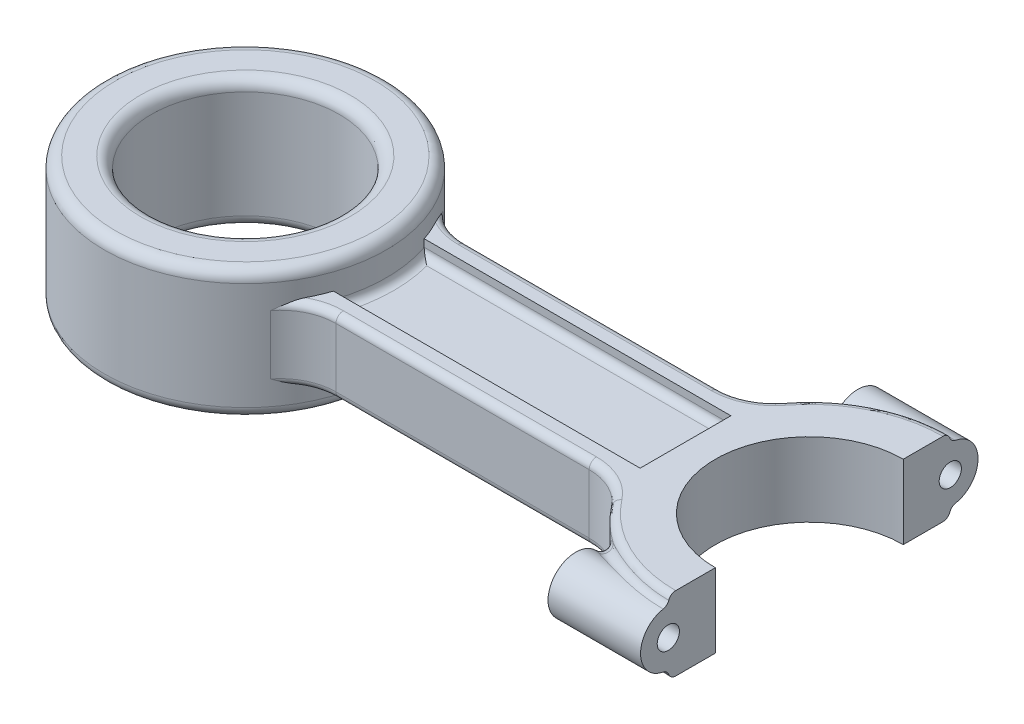
SolidWorks part; units mm, degrees
ref_plane "Front Plane" through (0, 0, 0) normal (0, 0, 1) x (1, 0, 0)
ref_plane "Top Plane" through (0, 0, 0) normal (0, 1, 0) x (1, 0, 0)
ref_plane "Right Plane" through (0, 0, 0) normal (1, 0, 0) x (0, 0, -1)
sketch "Sketch2" plane through (0, 0, 0) normal (0, 1, 0) x (1, 0, 0)
  line L0 (0, 0) -> (152.4, 0) construction
  line L1 (152.4, 38.1) -> (152.4, 25.4)
  line L2 (110.4076, -17.5) -> (41.9924, -17.5)
  line L4 (110.4076, 17.5) -> (41.9924, 17.5)
  line L6 (118.5568, -17.5) -> (33.8432, 17.5) construction
  line L7 (118.5568, 17.5) -> (33.8432, -17.5) construction
  line L8 (152.4, -25.4) -> (152.4, -38.1)
  circle A0 centre (0, 0) radius 25.4
  arc A1 (30.1301, 23.3192) -> (30.1301, -23.3192) centre (0, 0) ccw
  arc A2 (152.4, 25.4) -> (152.4, -25.4) centre (152.4, 0) ccw
  arc A3 (152.4, 38.1) -> (122.2699, 23.3192) centre (152.4, 0) ccw
  arc A4 (122.2699, -23.3192) -> (152.4, -38.1) centre (152.4, 0) ccw
  arc A5 (122.2699, 23.3192) -> (110.4076, 17.5) centre (110.4076, 32.5) cw
  arc A6 (110.4076, -17.5) -> (122.2699, -23.3192) centre (110.4076, -32.5) cw
  arc A7 (41.9924, -17.5) -> (30.1301, -23.3192) centre (41.9924, -32.5) ccw
  arc A8 (41.9924, 17.5) -> (30.1301, 23.3192) centre (41.9924, 32.5) cw
  point P7 (76.2, 0)
  dimension "D1" = 50.8
  dimension "D2" = 76.2
  dimension "D5" = 15
  dimension "D3" = 152.4
  dimension "D4" = 35
extrude "Boss-Extrude1" add sketch "Sketch2" along normal mid plane 20
sketch "Sketch3" plane through (0, 10, 0) normal (0, 1, 0) x (1, 0, 0)
  circle A0 centre (0, 0) radius 25.4 construction
  circle A1 centre (0, 0) radius 25.4
  circle A2 centre (0, 0) radius 38.1
extrude "Boss-Extrude2" add sketch "Sketch3" against normal blind 7.5 from offset 20 offset against normal yes
extrude "Boss-Extrude3" add sketch "Sketch3<2>" along normal blind 7.5
sketch "Sketch3<2>" plane through (0, 10, 0) normal (0, 1, 0) x (1, 0, 0) same geometry as "Sketch3"
sketch "Sketch4" plane through (0, 10, 0) normal (0, 1, 0) x (1, 0, 0)
  line L1 (38.1, 0) -> (127, 0) construction
  line L2 (36.0717, 12.2655) -> (118.9431, 12.2655)
  line L4 (36.0717, -12.2655) -> (118.9431, -12.2655)
  line L5 (118.9431, 12.2655) -> (118.9431, -12.2655)
  arc A0 (152.4, 25.4) -> (152.4, -25.4) centre (152.4, 0) ccw construction
  circle A1 centre (0, 0) radius 38.1 construction
  arc A2 (36.0717, -12.2655) -> (36.0717, 12.2655) centre (0, 0) ccw
  point P0 (0, 0)
extrude "Cut-Extrude1" cut sketch "Sketch4" against normal blind 4
mirror "Mirror1" about plane through (0, 0, 0) normal (0, 1, 0) of "Cut-Extrude1"
fillet "Fillet1" radius 3 4 edges at (0, -17.5, 25.4) (0, -17.5, 38.1) (0, 17.5, 38.1) (0, 17.5, 25.4)
fillet "Fillet2" radius 2 16 edges at (135.6198, 10, -34.2058) (117.014, 10, -19.0332) (35.386, 10, -19.0332) (135.6198, -10, -34.2058) (117.014, -10, -19.0332) (35.386, -10, -19.0332) (35.386, -10, 19.0332) (135.6198, -10, 34.2058) (117.014, -10, 19.0332) (35.386, 10, 19.0332) (135.6198, 10, 34.2058) (117.014, 10, 19.0332) (76.2, 10, -17.5) (76.2, -10, -17.5) (76.2, -10, 17.5) (76.2, 10, 17.5)
fillet "Fillet3" radius 2 8 edges at (77.5074, 6, 12.2655) (38.1, 6, 0) (77.5074, 6, -12.2655) (118.9431, 6, 0) (77.5074, -6, -12.2655) (38.1, -6, 0) (77.5074, -6, 12.2655) (118.9431, -6, 0)
sketch "Sketch5" plane through (152.4, 0, 0) normal (1, 0, 0) x (0, 0, -1)
  line L0 (-38.1, 8) -> (-38.1, -8) construction
  circle A0 centre (-38.1, 0) radius 7.5
  dimension "D1" = 15
extrude "Boss-Extrude4" add sketch "Sketch5" against normal blind 25
sketch "Sketch6" plane through (127.4, 0, 0) normal (-1, 0, 0) x (0, 0, 1)
  circle A0 centre (38.1, 0) radius 3
  dimension "D1" = 6
extrude "Cut-Extrude2" cut sketch "Sketch6" against normal through all
mirror "Mirror2" about plane through (0, 0, 0) normal (0, 0, 1) of "Boss-Extrude4", "Cut-Extrude2"
fillet "Fillet4" radius 2 2 edges at (129.7145, 0.3887, 30.6101) (129.7145, 0.3887, -30.6101)
